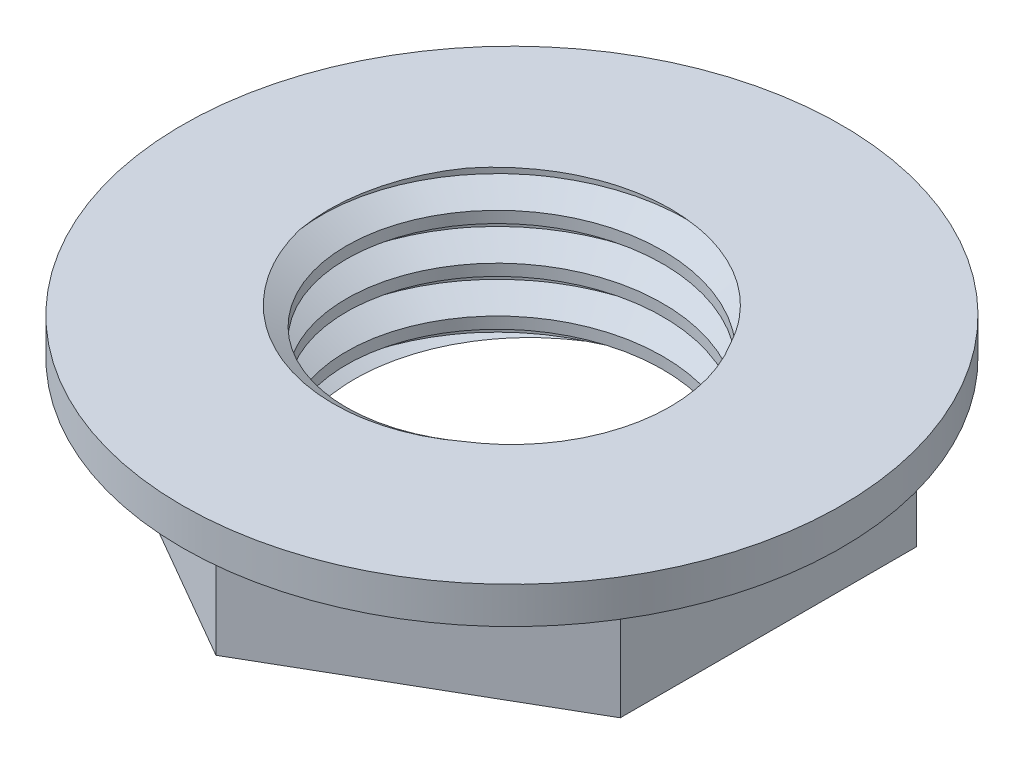
SolidWorks part; units mm, degrees
ref_plane "Front Plane" through (0, 0, 0) normal (0, 0, 1) x (1, 0, 0)
ref_plane "Top Plane" through (0, 0, 0) normal (0, 1, 0) x (1, 0, 0)
ref_plane "Right Plane" through (0, 0, 0) normal (1, 0, 0) x (0, 0, -1)
sketch "Sketch20" plane through (0, 0, 0) normal (0, 1, 0) x (-1, 0, 0)
  circle A0 centre (0, 0) radius 10
  circle A1 centre (0, 0) radius 18
extrude "Boss-Extrude5" add sketch "Sketch20" along normal blind 2
sketch "Sketch21" plane through (0, 0, 0) normal (0, -1, 0) x (-1, 0, 0)
  line L1 (0, 16.1658) -> (-14, 8.0829)
  line L2 (-14, 8.0829) -> (-14, -8.0829)
  line L3 (-14, -8.0829) -> (0, -16.1658)
  line L4 (0, -16.1658) -> (14, -8.0829)
  line L5 (14, -8.0829) -> (14, 8.0829)
  line L6 (14, 8.0829) -> (0, 16.1658)
  circle A0 centre (0, 0) radius 14 construction
  circle A1 centre (0, 0) radius 10
extrude "Boss-Extrude6" add sketch "Sketch21" along normal blind 6
thread "Thread1" pitch 2.5 method extrude trim with start face yes trim with end face yes profile "Thread Profile1" start angle 1, offset 3, length 12, pitch 2.5, diameter 20
ref_plane "Plane1" through (9.9985, -9, -0.1745) normal (0.0175, 0, 0.9998) x (0.9998, 0, -0.0175)
sketch "Thread Profile1" plane through (9.9985, -9, -0.1745) normal (0.0175, 0, 0.9998) x (0.9998, 0, -0.0175)
  line L0 (0, 0) -> (0, 2.5) construction
  line L11 (0, 0) -> (0, 2.1875)
  line L12 (0, 2.1875) -> (-1.3532, 1.4062)
  line L13 (-1.3532, 1.4062) -> (-1.3532, 0.7812)
  line L15 (-1.3532, 0.7812) -> (0, 0)
  line L17 (-1.3532, 1.0937) -> (0, 1.0937) construction
  point P2 (0, 0)
  dimension "Pitch" = 2.5
  dimension "Profile_Angle" = 60
  dimension "Profile_Land" = 0.625
  dimension "Profile_Height" = 1.3532
